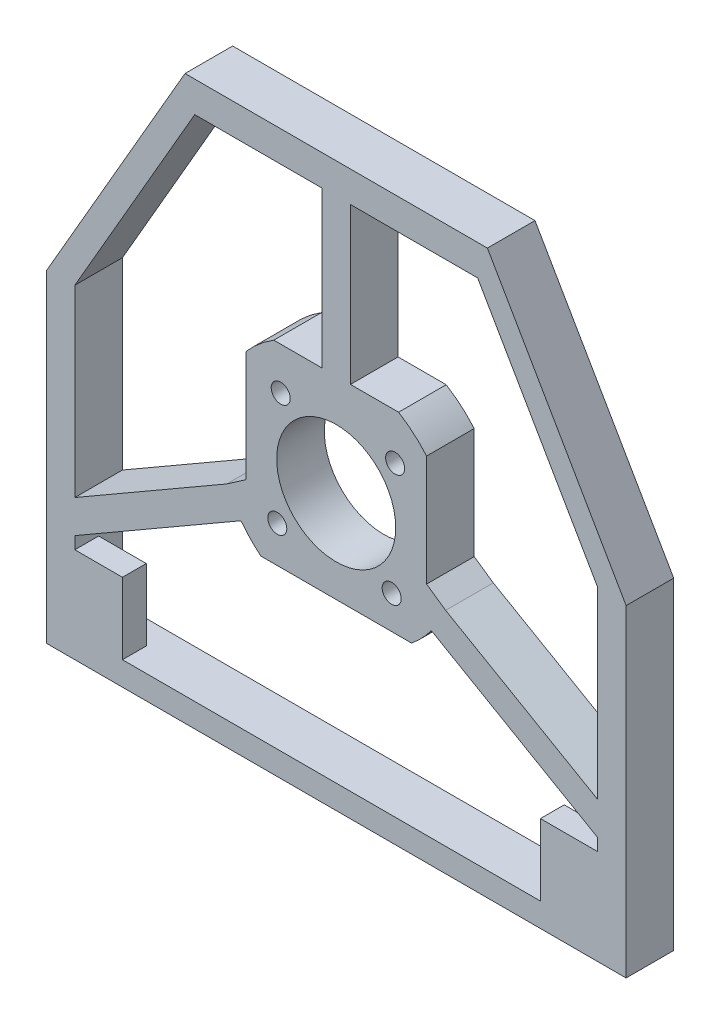
SolidWorks part; units mm, degrees
ref_plane "Front Plane" through (0, 0, 0) normal (0, 0, 1) x (1, 0, 0)
ref_plane "Top Plane" through (0, 0, 0) normal (0, 1, 0) x (1, 0, 0)
ref_plane "Right Plane" through (0, 0, 0) normal (1, 0, 0) x (0, 0, -1)
sketch "Sketch2" plane through (0, 0, 0) normal (0, 0, 1) x (1, 0, 0)
  line L0 (-100, -57.735) -> (50, 28.8675) construction
  line L1 (0, 115.4701) -> (-100, -57.735)
  line L2 (-100, -57.735) -> (100, -57.735)
  line L3 (100, -57.735) -> (0, 115.4701)
  line L4 (0, 105.4701) -> (-25.9808, 60.4701)
  line L5 (-91.3397, -52.735) -> (-60.8932, -52.735)
  line L6 (91.3397, -52.735) -> (60.8932, 0)
  line L7 (0, 115.4701) -> (0, -57.735) construction
  line L8 (100, -57.735) -> (-50, 28.8675) construction
  line L9 (-31.7543, 60.4701) -> (31.7543, 60.4701)
  line L10 (-60.8932, 0) -> (-60.8932, -52.735)
  line L11 (60.8932, 0) -> (60.8932, -52.735)
  line L12 (-60.8932, 0) -> (-60.8932, 10)
  line L13 (-60.8932, -52.735) -> (-60.8932, -57.735)
  line L14 (60.8932, -52.735) -> (60.8932, -57.735)
  line L15 (60.8932, 0) -> (60.8932, 10)
  line L16 (-29.7078, 54.0147) -> (-3, 54.0147)
  line L17 (-54.8932, 10.3923) -> (-54.8932, -28.2285)
  line L18 (54.8932, 10.3923) -> (54.8932, -28.2285)
  line L19 (-29.7078, 54.0147) -> (-54.8932, 10.3923)
  line L20 (25.9808, 60.4701) -> (0, 105.4701)
  line L21 (54.8932, 10.3923) -> (29.7078, 54.0147)
  line L22 (60.8932, -52.735) -> (91.3397, -52.735)
  line L23 (-54.8932, -52.735) -> (54.8932, -52.735)
  line L24 (-60.8932, 0) -> (-91.3397, -52.735)
  line L25 (-54.8932, -28.2285) -> (-22.9942, -9.8116)
  line L26 (-54.8932, -35.1567) -> (-19.9942, -15.0077)
  line L27 (-3, 54.0147) -> (-3, 24.8193)
  line L28 (3, 54.0147) -> (3, 24.8193)
  line L29 (24.88, 2.4466) -> (25, 0)
  line L30 (19.9942, -15.0077) -> (54.8932, -35.1567)
  line L31 (22.9942, -9.8116) -> (54.8932, -28.2285)
  line L32 (-54.8932, -35.1567) -> (-54.8932, -52.735)
  line L33 (54.8932, -35.1567) -> (54.8932, -52.735)
  line L34 (3, 54.0147) -> (29.7078, 54.0147)
  circle A0 centre (0, 0) radius 57.735 construction
  circle A1 centre (0, 0) radius 52.735 construction
  circle A2 centre (0, 0) radius 25
  point P19 (60.8932, -35.1567)
  point P26 (-60.8932, -34.768)
  point P31 (0, 54.0147)
  point P32 (0, 60.4701)
  point P33 (54.8932, -31.7432)
  point P34 (60.8932, -35.1567)
  dimension "D6" = 50
  dimension "D1" = 200
  dimension "D2" = 10
  dimension "D3" = 45
  dimension "D4" = 6
  dimension "D5" = 6
  dimension "D7" = 3
  dimension "D8" = 3
  dimension "D9" = 3
  dimension "D10" = 3
  dimension "D11" = 3
  dimension "D12" = 3
extrude "Boss-Extrude1" add sketch "Sketch2" along normal blind 10 contours L11 L15 L3 L9 L1 L12 L10 L13 L2 L14 A2 L28 L34 L21 L18 L31 L30 L33 L23 L32 L26 L25 L17 L19 L16 L27 | L29 A2 region at (-28.8675, 58.7729, 0) region at (-0.0006, 0, 0)
sketch "Sketch4" plane through (0, 0, 10) normal (0, 0, 1) x (1, 0, 0)
  line L0 (-11.6531, 12.3776) -> (11.6531, -12.3776) construction
  line L1 (-12.3776, -11.6531) -> (12.3776, 11.6531) construction
  line L2 (-3, 24.8193) -> (-3, -24.8193) construction
  line L3 (3, 24.8193) -> (3, -24.8193) construction
  line L4 (-3, 21.2891) -> (-13.1063, 21.2891)
  line L5 (3, 21.2891) -> (13.1063, 21.2891)
  line L6 (-18.9891, 16.2608) -> (-18.9891, -7.0373)
  line L7 (-3, 21.2891) -> (-3, 24.8193)
  line L8 (3, 21.2891) -> (3, 24.8193)
  line L9 (-18.9891, -7.0373) -> (-23.9891, -7.0373)
  line L10 (18.9891, 16.2608) -> (18.9891, -7.0373)
  line L11 (18.9891, -7.0373) -> (23.9891, -7.0373)
  line L12 (-15.8323, -19.3478) -> (15.8323, -19.3478)
  line L13 (-22.9942, -9.8116) -> (-18.9891, -7.0373)
  line L14 (22.9942, -9.8116) -> (18.9891, -7.0373)
  arc A0 (-13.6606, -10.1187) -> (-10.9234, -13.0261) centre (0, 0) ccw
  circle A1 centre (-11.6531, 12.3776) radius 2
  circle A2 centre (-12.3776, -11.6531) radius 2
  circle A3 centre (11.6531, -12.3776) radius 2
  circle A4 centre (12.3776, 11.6531) radius 2
  arc A5 (-10.1187, 13.6606) -> (-13.0261, 10.9234) centre (0, 0) ccw
  arc A6 (13.6606, 10.1187) -> (10.9234, 13.0261) centre (0, 0) ccw
  arc A7 (10.1187, -13.6606) -> (13.0261, -10.9234) centre (0, 0) ccw
  arc A8 (-19.9942, -15.0077) -> (19.9942, -15.0077) centre (0, 0) ccw construction
  arc A9 (-3, 24.8193) -> (-22.9942, -9.8116) centre (0, 0) ccw construction
  arc A10 (24.88, 2.4466) -> (3, 24.8193) centre (0, 0) ccw construction
  arc A11 (22.9942, -9.8116) -> (25, 0) centre (0, 0) ccw construction
  circle A12 centre (0, 0) radius 12.5
  point P3 (-11.6531, 12.3776)
  point P4 (12.3776, 11.6531)
  point P5 (11.6531, -12.3776)
  point P6 (-12.3776, -11.6531)
  point P11 (0, 0)
  arc M6 (-3, 24.8193) -> (-22.9942, -9.8116) centre (0, 0) ccw
  arc M12 (22.9942, -9.8116) -> (25, 0) centre (0, 0) ccw
  line M13 (25, 0) -> (24.88, 2.4466)
  arc M14 (24.88, 2.4466) -> (3, 24.8193) centre (0, 0) ccw
  arc M19 (-19.9942, -15.0077) -> (19.9942, -15.0077) centre (0, 0) ccw
  dimension "D1" = 34
  dimension "D3" = 4
  dimension "D4" = 4
  dimension "D5" = 4
  dimension "D6" = 4
  dimension "D9" = 25
  dimension "D2" = 90
  dimension "D7" = 5
  dimension "D8" = 5
extrude "Cut-Extrude1" cut sketch "Sketch4" against normal blind 10 contours A1 A5 | A1 | A4 | A3 | A2 region at (-11.0569, 11.7444, 10)
extrude "Cut-Extrude2" cut sketch "Sketch4<4>" against normal blind 10 contours L4 L7 M6 | L8 L5 M14 | L9 L6 M6 | L10 L11 M12 M13 M14 | L12 M19 region at (-21.5753, 2.6112, 10) region at (-6.7009, 22.6182, 10) region at (6.7009, 22.6182, 10) region at (21.5738, 2.6119, 10) region at (0, -21.6321, 10)
sketch "Sketch4<4>" plane through (0, 0, 10) normal (0, 0, 1) x (1, 0, 0) same geometry as "Sketch4"
extrude "Cut-Extrude3" cut sketch "Sketch4<5>" against normal blind 10 contours A12 region at (0, 0, 10)
sketch "Sketch4<5>" plane through (0, 0, 10) normal (0, 0, 1) x (1, 0, 0) same geometry as "Sketch4"
extrude "Cut-Extrude4" cut sketch "Sketch4<6>" against normal blind 10 contours L13 L9 M6 | L14 L11 M12 region at (-22.0092, -7.9678, 10) region at (22.0092, -7.9678, 10)
sketch "Sketch4<6>" plane through (0, 0, 10) normal (0, 0, 1) x (1, 0, 0) same geometry as "Sketch4"
sketch "Sketch5" plane through (-54.8932, 0, 0) normal (1, 0, 0) x (0, 0, -1)
  line L1 (-5, -52.735) -> (-10, -52.735)
  line L2 (-5, -52.735) -> (-5, -37.735)
  line L3 (-5, -37.735) -> (-10, -37.735)
  line L4 (-10, -52.735) -> (-10, -37.735)
  line L5 (-5, -52.735) -> (-10, -37.735) construction
  line L6 (-5, -37.735) -> (-10, -52.735) construction
  line L7 (-10, -52.735) -> (0, -52.735) construction
  line L8 (-10, -35.1567) -> (-10, -52.735) construction
  point P0 (-7.5, -45.235)
  dimension "D1" = 5
  dimension "D2" = 15
extrude "Boss-Extrude2" add sketch "Sketch5" along normal blind 10
sketch "Sketch6" plane through (54.8932, 0, 0) normal (-1, 0, 0) x (0, 0, 1)
  line L0 (0, -35.1567) -> (0, -52.735) construction
  line L1 (5, -52.735) -> (0, -52.735)
  line L2 (5, -52.735) -> (5, -37.735)
  line L3 (5, -37.735) -> (0, -37.735)
  line L4 (0, -52.735) -> (0, -37.735)
  line L5 (5, -52.735) -> (0, -37.735) construction
  line L6 (5, -37.735) -> (0, -52.735) construction
  line L7 (10, -52.735) -> (0, -52.735) construction
  point P0 (2.5, -45.235)
  dimension "D1" = 5
  dimension "D2" = 15
sketch "Sketch7" plane through (54.8932, 0, 0) normal (-1, 0, 0) x (0, 0, 1)
  line L1 (10, -52.735) -> (5, -52.735)
  line L2 (10, -52.735) -> (10, -37.735)
  line L3 (10, -37.735) -> (5, -37.735)
  line L4 (5, -52.735) -> (5, -37.735)
  line L5 (10, -52.735) -> (5, -37.735) construction
  line L6 (10, -37.735) -> (5, -52.735) construction
  line L8 (5, -52.735) -> (0, -52.735) construction
  line L9 (10, -35.1567) -> (10, -52.735) construction
  point P0 (7.5, -45.235)
  dimension "D1" = 5
  dimension "D2" = 15
extrude "Boss-Extrude4" add sketch "Sketch7" along normal blind 12
